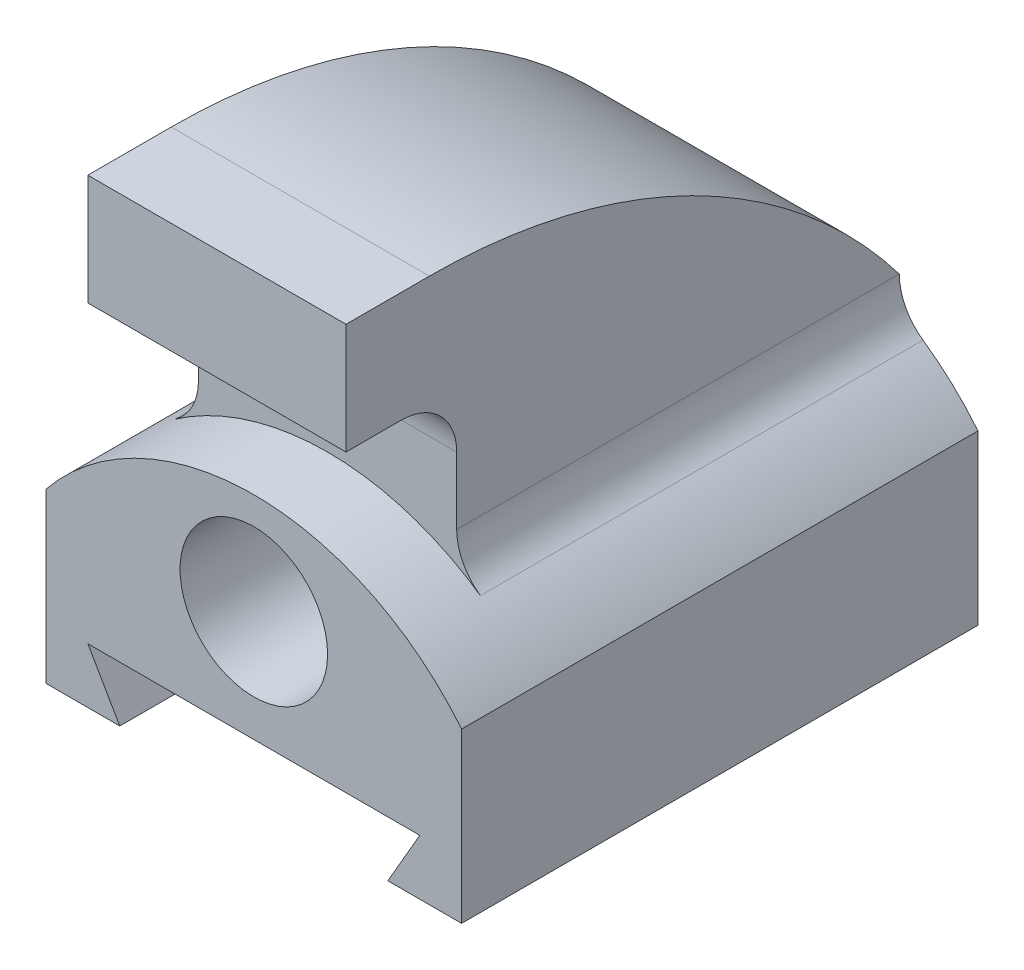
SolidWorks part; units mm, degrees
ref_plane "Front Plane" through (0, 0, 0) normal (0, 0, 1) x (1, 0, 0)
ref_plane "Top Plane" through (0, 0, 0) normal (0, 1, 0) x (1, 0, 0)
ref_plane "Right Plane" through (0, 0, 0) normal (1, 0, 0) x (0, 0, -1)
sketch "Sketch2" plane through (0, 0, 0) normal (0, 0, 1) x (1, 0, 0)
  line L0 (-28.575, 0) -> (28.575, 0)
  line L1 (0, 0) -> (0, 56.3128) construction
  line L2 (28.575, -9.525) -> (35.7757, -9.525)
  line L3 (35.7757, -9.525) -> (35.7757, 19.45)
  line L4 (28.575, 0) -> (23.0757, -9.525)
  line L5 (23.0757, -9.525) -> (28.575, -9.525)
  line L6 (-23.0757, -9.525) -> (-28.575, -9.525)
  line L7 (-28.575, 0) -> (-23.0757, -9.525)
  line L8 (-35.7757, -9.525) -> (-35.7757, 19.45)
  line L9 (-28.575, -9.525) -> (-35.7757, -9.525)
  arc A0 (35.7757, 19.45) -> (-35.7757, 19.45) centre (0, -9.525) ccw
  circle A1 centre (0, 19.05) radius 12.7
  dimension "D7" = 9.525
  dimension "D6" = 46.0375
  dimension "D9" = 25.4
  dimension "D1" = 9.525
  dimension "D2" = 60
  dimension "D3" = 28.575
  dimension "D4" = 12.7
  dimension "D5" = 23.0757
  dimension "D8" = 19.05
extrude "Boss-Extrude1" add sketch "Sketch2" along normal mid plane 88.9
sketch "Sketch5" plane through (0, 0, -44.45) normal (0, 0, -1) x (-1, 0, 0)
  line L0 (0, 36.5125) -> (0, 76.824) construction
  line L1 (-22.225, 36.0725) -> (-22.225, 57.15)
  line L2 (-22.225, 57.15) -> (-22.225, 76.2)
  line L3 (-22.225, 76.2) -> (22.225, 76.2)
  line L4 (-23.0757, -9.525) -> (-35.7757, -9.525) construction
  line L5 (22.225, 57.15) -> (22.225, 76.2)
  line L6 (22.225, 36.0725) -> (22.225, 57.15)
  line L7 (-22.225, 57.15) -> (22.225, 57.15)
  line L8 (-35.7757, -9.525) -> (-35.7757, 19.45) construction
  line L9 (35.7757, 19.45) -> (35.7757, -9.525) construction
  arc A0 (35.7757, 19.45) -> (-35.7757, 19.45) centre (0, -9.525) ccw construction
  arc A1 (22.225, 30.7925) -> (-22.225, 30.7925) centre (0, -9.525) ccw
  arc A2 (-26.3071, 28.2558) -> (-35.7757, 19.45) centre (0, -9.525) ccw
  arc A3 (26.3071, 28.2558) -> (35.7757, 19.45) centre (0, -9.525) cw
  arc A4 (-22.225, 36.0725) -> (-26.3071, 28.2558) centre (-31.75, 36.0725) cw
  arc A5 (22.225, 36.0725) -> (26.3071, 28.2558) centre (31.75, 36.0725) ccw
  point P16 (0, 76.2)
  arc M9 (35.7757, 19.45) -> (-35.7757, 19.45) centre (0, -9.525) ccw
  dimension "D4" = 9.525
  dimension "D1" = 22.225
  dimension "D2" = 19.05
  dimension "D3" = 85.725
extrude "Boss-Extrude3" add sketch "Sketch5" against normal blind 76.2 contours L7 L0 L3 L2 | L0 L7 L5 L3 | L0 L6 L7 M9 | A1 L0 L7 L1 region at (11.6716, 45.7211, -44.45) region at (-11.6716, 45.7211, -44.45) region at (11.1125, 66.675, -44.45) region at (-11.1125, 66.675, -44.45)
extrude "Boss-Extrude4" add sketch "Sketch5<3>" against normal blind 95.25 contours L7 L0 L3 L2 | L0 L7 L5 L3 region at (11.1125, 66.675, -44.45) region at (-11.1125, 66.675, -44.45)
sketch "Sketch5<3>" plane through (0, 0, -44.45) normal (0, 0, -1) x (-1, 0, 0) same geometry as "Sketch5"
sketch "Sketch6" plane through (22.225, 0, 0) normal (1, 0, 0) x (0, 0, -1)
  line L1 (44.45, 36.0725) -> (44.45, 76.2) construction
  line L2 (-50.8, 76.2) -> (44.45, 76.2)
  line L3 (44.45, 76.2) -> (44.45, 36.0725)
  circle A1 centre (-36.4431, -25.4) radius 101.6
  line M4 (44.45, 36.0725) -> (44.45, 76.2)
  line M5 (44.45, 76.2) -> (-50.8, 76.2)
  dimension "D1" = 203.2
extrude "Cut-Extrude2" cut sketch "Sketch6" against normal through all contours A1 M4 M5 region at (22.225, 64.7176, -25.1119)
fillet "Fillet1" radius 9.525 1 edges at (0, 57.15, 31.75)
